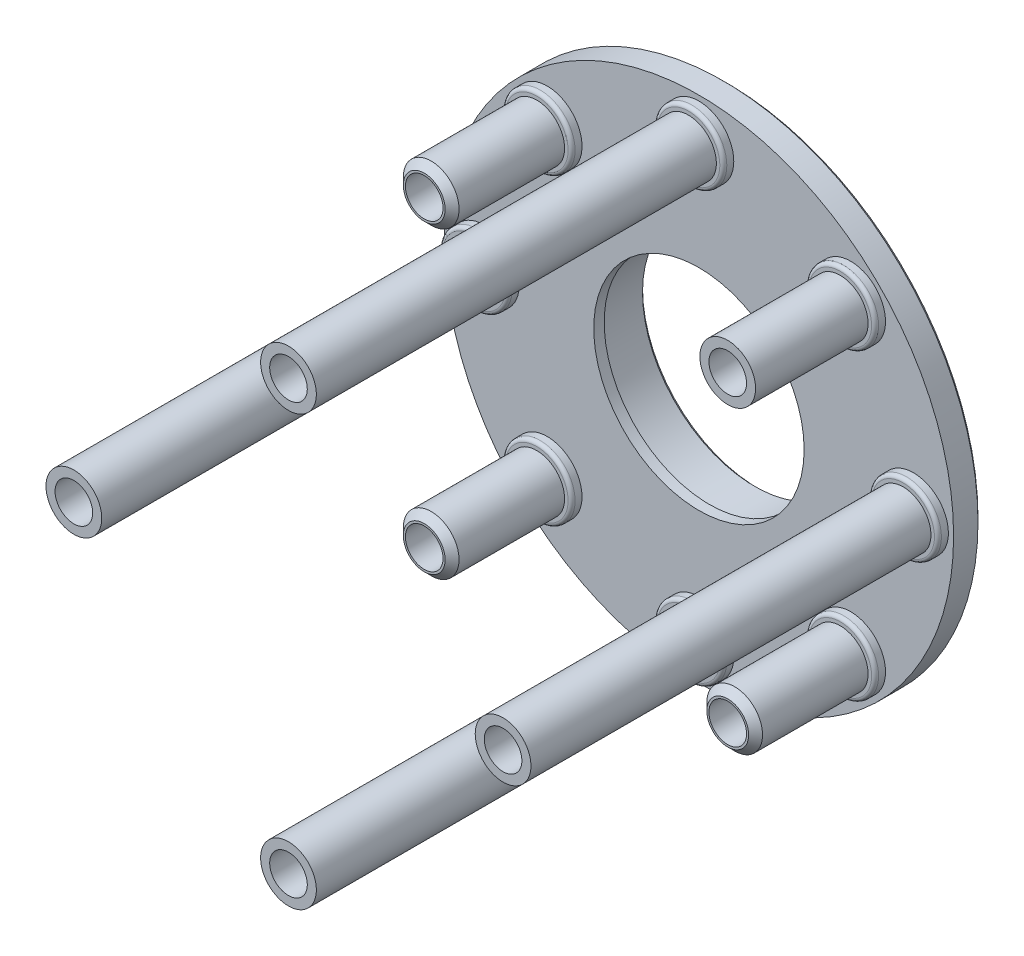
SolidWorks part; units mm, degrees
material "PLA"
ref_plane "Front Plane" through (0, 0, 0) normal (0, 0, 1) x (1, 0, 0)
ref_plane "Top Plane" through (0, 0, 0) normal (0, 1, 0) x (1, 0, 0)
ref_plane "Right Plane" through (0, 0, 0) normal (1, 0, 0) x (0, 0, -1)
sketch "Sketch1" plane through (0, 0, 0) normal (0, 0, 1) x (1, 0, 0)
  circle A0 centre (0, 0) radius 36.55
  circle A1 centre (0, 0) radius 30.8 construction
  circle A2 centre (0, 30.8) radius 2.7
  circle A3 centre (30.8, 0) radius 2.7
  circle A78 centre (0, -30.8) radius 2.7
  circle A79 centre (0, 30.8) radius 4.25 construction
  circle A80 centre (0, 0) radius 35.05 construction
  circle A94 centre (-30.8, 0) radius 2.7
  point P15 (0, 0)
  dimension "D2" = 61.6
  dimension "D3" = 5.4
  dimension "D5" = 8.5
  dimension "D1" = 1.5
  dimension "D4" = 4
extrude "Boss-Extrude1" add sketch "Sketch1" along normal blind 4
sketch "Sketch2" plane through (0, 0, 4) normal (0, 0, 1) x (1, 0, 0)
  circle A0 centre (0, 30.8) radius 4
  circle A2 centre (0, 30.8) radius 2.7 construction
  circle A5 centre (0, 30.8) radius 2.7
  point P15 (0, 0)
  dimension "D1" = 8
extrude "Boss-Extrude2" add sketch "Sketch2" along normal blind 58.9087
sketch "Sketch3" plane through (0, 0, 4) normal (0, 0, 1) x (1, 0, 0)
  arc A2 (5, 30.8) -> (5, 30.8) centre (0, 30.8) ccw
  circle A3 centre (0, 30.8) radius 5
  circle M5 centre (0, 30.8) radius 4
extrude "Boss-Extrude3" add sketch "Sketch3" along normal blind 1.5 contours A3 M5 region at (-4.8586, 30.8, 4)
sketch "Sketch4" plane through (0, 0, 4) normal (0, 0, 1) x (1, 0, 0)
  line L0 (0, 0) -> (-25.8448, 25.8448) construction
  line L1 (0, 0) -> (0, 30.8) construction
  circle A0 centre (0, 0) radius 36.55 construction
  circle A1 centre (0, 0) radius 36.55
  circle A2 centre (0, 30.8) radius 14 construction
  circle A6 centre (0, 0) radius 30.8 construction
  arc A8 (-15.3152, 33.1866) -> (-10.2972, 19.2148) centre (0, 30.8) ccw
  circle A9 centre (0, 0) radius 21.8
  circle A11 centre (0, 0) radius 16.8 construction
  arc A13 (-33.1866, 15.3152) -> (-19.2148, 10.2972) centre (-30.8, 0) cw
  circle A16 centre (0, 30.8) radius 15.5 construction
  point P15 (0, 0)
  point P25 (0, 0)
  dimension "D1" = 28
  dimension "D5" = 33.6
  dimension "D4" = 5
  dimension "D2" = 45
  dimension "D3" = 1.5
extrude "Boss-Extrude4" [suppressed] add sketch "Sketch4" along normal blind 58.9087 contours A1 A13 A9 A8
sketch "Sketch12" [suppressed] plane through (0, 0, 37.8382) normal (0, 0, 1) x (1, 0, 0)
  arc A0 (-11.2345, 15.816) -> (-15.816, 11.2345) centre (0, 0) ccw construction
  arc A1 (-11.2345, 15.816) -> (-15.816, 11.2345) centre (0, 0) ccw
  dimension "D1" = 6.4791
fillet "Fillet2" radius 0.5 1 edges at (5, 30.8, 5.5)
fillet "Fillet5" [suppressed] radius 1.6198
pattern_circular "CirPattern1" count 8 over 360 about axis through (0, 0, 4) along (0, 0, -1) of "Fillet2", "Boss-Extrude3", "Boss-Extrude2" reverse direction yes
ref_plane "Plane1" through (0, 0, 62.9087) normal (0, 0, 1) x (1, 0, 0)
chamfer "Chamfer1" distance 0.5 angle 45 1 edges at (36.55, 0, 0)
sketch "Sketch9" plane through (0, 0, 4) normal (0, 0, 1) x (1, 0, 0)
  circle A0 centre (0, 0) radius 8
  dimension "D1" = 16
extrude "Cut-Extrude4" cut sketch "Sketch9" against normal through all
sketch "Sketch10" plane through (0, 0, 0) normal (0, 0, -1) x (-1, 0, 0)
  circle A0 centre (0, 0) radius 8 construction
  circle A1 centre (0, 0) radius 8
  circle A2 centre (0, 0) radius 6.5
  dimension "D1" = 1.5
extrude "Boss-Extrude7" add sketch "Sketch10" against normal blind 6.5
sketch "Sketch13" plane through (0, 0, 0) normal (0, 1, 0) x (1, 0, 0)
  line L0 (0, 0) -> (0, -62.9087) construction
  line L1 (-4, -62.9087) -> (4, -62.9087) construction
  line L2 (19.0789, -4) -> (24.4789, -4) construction
  line L3 (-35, 0.5) -> (-45.6, -4) construction
  line L4 (-41.7615, -4) -> (-32.3392, 0)
  line L7 (36.05, 0) -> (-36.05, 0) construction
  line L8 (0, -4) -> (-45.6, -4) construction
  line L9 (-32.3392, 0) -> (-41.7615, 0)
  line L10 (-41.7615, 0) -> (-41.7615, -4)
  dimension "D1" = 35
  dimension "D2" = 45.6
  dimension "D3" = 4.5
  dimension "D4" = 1.5
sketch "Sketch14" plane through (0, 0, 4) normal (0, 0, 1) x (1, 0, 0)
  circle A0 centre (0, 0) radius 16.1
  circle A1 centre (0, 0) radius 6.5 construction
  dimension "D1" = 32.2
extrude "Cut-Extrude5" cut sketch "Sketch14" against normal through all both and the other way through all
sketch "Sketch15" plane through (0, 0, 4) normal (0, 0, 1) x (1, 0, 0)
  circle A0 centre (0, 0) radius 16.1
  circle A1 centre (0, 0) radius 15.1
  circle A2 centre (0, 0) radius 16.1 construction
  dimension "D1" = 1
extrude "Boss-Extrude8" add sketch "Sketch15" against normal blind 1.5
sketch "Sketch16" plane through (0, 0, 0) normal (0, 0, -1) x (-1, 0, 0)
  circle A0 centre (0, 0) radius 18.1
  circle A1 centre (0, 0) radius 16.1 construction
  circle M1 centre (0, 0) radius 16.1
extrude "Boss-Extrude9" add sketch "Sketch16" along normal blind 4.5 contours A0 M1 region at (17.5881, 0, 0)
chamfer "Chamfer3" distance 2 distance2 4.5 1 edges at (18.1, 0, 0) first distance on face at (18.1, 0, 0)
sketch "Sketch5" [suppressed] plane through (0, 0, 32.8234) normal (0, 0, 1) x (1, 0, 0)
  line L0 (0, 0) -> (-22.4506, 22.4506) construction
  line L1 (0, 0) -> (0, 26) construction
  circle A3 centre (-19.6222, 19.6222) radius 1.7
  circle A4 centre (0, 0) radius 31.75 construction
  arc A5 (-13.189, 28.881) -> (-28.881, 13.189) centre (0, 0) ccw construction
  dimension "D2" = 3.4
  dimension "D1" = 4
  dimension "D3" = 45
extrude "Cut-Extrude1" [suppressed] cut sketch "Sketch5" against normal through all
sketch "Sketch7" plane through (0, 0, 0) normal (0, 0, -1) x (-1, 0, 0)
  circle A0 centre (0, 30.8) radius 4.45
  circle A1 centre (0, 0) radius 30.8 construction
  point P15 (0, 0)
  dimension "D1" = 8.9
extrude "Cut-Extrude3" cut sketch "Sketch7" against normal blind 5 and the other way through all
sketch "Sketch6" [suppressed] plane through (0, 0, 0) normal (0, 0, -1) x (-1, 0, 0)
  circle A0 centre (19.6222, 19.6222) radius 2.95
  dimension "D1" = 5.9
extrude "Cut-Extrude2" [suppressed] cut sketch "Sketch6" against normal blind 3 and the other way through all
pattern_circular "CirPattern2" count 8 over 360 about axis through (0, 0, 4) along (0, 0, -1) of "Cut-Extrude3" reverse direction yes
chamfer "Chamfer4" distance 0.5 angle 45 1 edges at (-16.1, 0, -4.5)
sketch "Sketch17" plane through (0, 0, 62.9087) normal (0, 0, 1) x (1, 0, 0)
  circle A0 centre (-21.7789, 21.7789) radius 6.5962
extrude "Cut-Extrude6" cut sketch "Sketch17" against normal blind 41.2609
pattern_circular "CirPattern3" count 4 over 360 about axis through (0, 0, 4) along (0, 0, 1) of "Cut-Extrude6"
chamfer "Chamfer5" distance 1 angle 45 3 edges at (25.7789, -21.7789, 21.6477) (-17.7789, 21.7789, 21.6477) (-17.7789, -21.7789, 21.6477)
equation "\"Nr_s\" = 116"
equation "\"module\" = 0.7"
equation "\"pressure_angle\" = 20.0"
equation "\"h_a\" = 0.7"
equation "\"h_f\" = 0.875"
equation "\"clr_tip_root\" = 0.17500000000000004"
equation "\"dp_r_s\" = 81.19999999999999"
equation "\"db_r\"= \"dp_r_s\" * cos ( \"pressure_angle\" )'base CD"
equation "\"bearing_ID\" = 70"
equation "\"bearing_OD\" = 90"
equation "\"bearing_height\" = 10"
equation "\"clearance_planet\" = 1.5"
equation "\"case_dist\" = 6.5"
equation "\"Motor_case_OD_max\" = 131.3"
equation "\"case_mounting_PCD\" = 123.8"
equation "\"bearing mount thickness\" = 8"
equation "\"case_mounting_hole_dia\" = 3"
equation "\"output_mounting_PCD\" = 98"
equation "\"output_mounting_hole_dia\" = 4"
equation "\"clearance_case_mount_holes_shell_thickness\" = 1"
equation "\"motor_case_OD_base\" = 121.8"
equation "\"sec_carrier_thickness\" = 5"
equation "\"sun_coupler_hub_thickness\" = 4"
equation "\"clearance_sun_coupler_sec_carrier\" = 1.5"
equation "\"clearance_motor_and_case\" = 5"
equation "\"motor_OD\" = 106.8"
equation "\"Motor_case_thickness\" = 2.5"
equation "\"Motor_case_ID\" = 116.8"
equation "\"case_mounting_hole_shift\" = 1.0"
equation "\"output_mounting_nut_wrench_size\" = 7"
equation "\"output_mounting_nut_thickness\" = 3.2"
equation "\"case_mounting_hole_allen_socket_dia\" = 5.5"
equation "\"output_mounting_nut_depth\" = 3"
equation "\"case_mounting_bolt_depth\" = 4.5"
equation "\"Ns\" = 48"
equation "\"Np_b\" = 40"
equation "\"ring_radial_thickness\" = 5"
equation "\"ring_OD\"= \"Nr_s\" * \"module\" + \"ring_radial_thickness\" * 2"
equation "\"ring_to_chamfer_clearance\" = 1.5"
equation "\"Motor_case_OD_base_to_chamfer\" = 5"
equation "\"pattern_offset_from_motor_case_OD_base\" = 3"
equation "\"pattern_bulge_dia\" = 3"
equation "\"pattern_num_bulge\" = 18"
equation "\"pattern_depth\" = 2"
equation "\"motor_height\" = 47.6"
equation "\"case_mounting_wrench_size\" = 5.5"
equation "\"case_mounting_nut_clearance\" = 2"
equation "\"base_plate_thickness\" = 4"
equation "\"case_mounting_nut_thickness\" = 2.4"
equation "\"case_mounting_surface_height\" = 4"
equation "\"motor_mount_hole_PCD\" = 40"
equation "\"motor_mount_hole_dia\" = 5"
equation "\"motor_mount_hole_num\" = 4"
equation "\"central_hole_offset_from_motor_mount_PCD\" = 5"
equation "\"wire_slot_dist_from_center\" = 45.5"
equation "\"wire_slot_length\" = 10"
equation "\"wire_slot_radius\" = 3"
equation "\"driver_upper_holes_dist_from_center\" = 29"
equation "\"driver_lower_holes_dist_from_center\" = 13"
equation "\"driver_side_holes_dist_from_center\" = 22.5"
equation "\"driver_mount_holes_dia\" = 3"
equation "\"driver_mount_inserts_OD\" = 4.8"
equation "\"driver_mount_thickness\" = 1.5"
equation "\"driver_mount_height\" = 6"
equation "\"air_flow_hole_offset\" = 3"
equation "\"num_planet\" = 4"
equation "\"planet_pin_bolt_dia\" = 5"
equation "\"planet_pin_socket_head_dia\" = 8.5"
equation "\"carrier_PCD\" = 61.599999999999994"
equation "\"D2@Sketch1\"=\"carrier_PCD\""
equation "\"D3@Sketch1\"=\"planet_pin_bolt_dia\" + \"tight_clearance_3DP\""
equation "\"D4@Sketch1\"=\"num_planet\""
equation "\"D1@Boss-Extrude2\" = \"fw_p_s\" + \"clearance_planet\" * 2 + \"fw_p_b\""
equation "\"D1@Boss-Extrude3\"=\"clearance_planet\""
equation "\"D1@Sketch4\"=\"Np_b\"*\"module\""
equation "\"D3@Sketch4\"=\"clearance_planet\""
equation "\"D1@Boss-Extrude4\" = \"fw_p_s\" + \"clearance_planet\" * 2 + \"fw_p_b\""
equation "\"D1@Fillet2\"=\"clearance_planet\"/3"
equation "\"D1@CirPattern1\"=2*\"num_planet\""
equation "\"D1@CirPattern2\"=2*\"num_planet\""
equation "\"D1@Boss-Extrude7\"=\"bearing_height\"+ \"carrier_bearing_step_width\" - \"sun_shaft_bearing_width\""
equation "\"planet_shaft_dia\" = 8"
equation "\"D1@Sketch2\"= \"planet_shaft_dia\""
equation "\"planet_shaft_step_offset\" = 1"
equation "\"D1@Sketch3\"=\"planet_shaft_step_offset\""
equation "\"carrier_trapezoidal_support_sun_offset\" = 5"
equation "\"D4@Sketch4\"=\"carrier_trapezoidal_support_sun_offset\""
equation "\"carrier_trapezoidal_support_hole_PCD_offset_bearing_ID\" = 4"
equation "\"carrier_trapezoidal_support_hole_dia\" = 3"
equation "\"D2@Sketch5\"=\"carrier_trapezoidal_support_hole_dia\" + \"tight_clearance_3DP\""
equation "\"D1@Cut-Extrude2\"=\"carrier_trapezoidal_support_hole_dia\""
equation "\"carrier_trapezoidal_support_hole_socket_head_dia\" = 5.5"
equation "\"D1@Sketch6\"=\"carrier_trapezoidal_support_hole_socket_head_dia\" +  \"tight_clearance_3DP\""
equation "\"D1@Cut-Extrude3\"=\"planet_pin_bolt_dia\""
equation "\"D1@Sketch7\"=\"planet_pin_socket_head_dia\" + \"tight_clearance_3DP\""
equation "\"carrier_bearing_step_width\" = 1.5"
equation "\"standard_clearance_1_5mm\" = 1.5"
equation "\"standard_fillet_1_5mm\" = 1.5"
equation "\"sun_shaft_bearing_OD\" = 16"
equation "\"D1@Sketch9\"=\"sun_shaft_bearing_OD\""
equation "\"D1@Sketch10\"=\"standard_clearance_1_5mm\""
equation "\"sun_shaft_bearing_width\" = 5"
equation "\"standard_bearing_insertion_chamfer\" = 0.5"
equation "\"D1@Chamfer1\"=\"standard_bearing_insertion_chamfer\""
equation "\"D5@Sketch4\"=\"Ns\"*\"module\""
equation "\"D1@Sketch5\"=\"carrier_trapezoidal_support_hole_PCD_offset_bearing_ID\""
equation "\"D1@Plane1\" = \"fw_p_s\" + \"clearance_planet\" * 2 + \"fw_p_b\""
equation "\"D2@Sketch4\"=180/\"num_planet\""
equation "\"D3@Sketch5\"=180/\"num_planet\""
equation "\"carrier_trapezoidal_support_hole_wrench_size\" = 5.5"
equation "\"planet_pin_bolt_wrench_size\" = 8"
equation "\"pressure angle\" = 20.0"
equation "\"h_b\" = 0.875"
equation "\"dp_s\" = 33.599999999999994"
equation "\"db_s\" = 31.57367205840652"
equation "\"fw_s_calc\" = 5.685933367726717"
equation "\"alpha_s\" = 0.8539582918412343"
equation "\"beta_s\" = 2.0420834163175314"
equation "\"dp_p_b\" = 28.0"
equation "\"db_p_b\" = 26.311393382005434"
equation "\"fw_p_s\" = 25.912913082891553"
equation "\"alpha_p_b\" = 0.8539582918412485"
equation "\"beta_p_b\" = 2.792083416317503"
equation "\"planet_bearing_OD\" = 12"
equation "\"planet_bearing_width\" = 3.5"
equation "\"planet_bore\" = 10"
equation "\"motor_output_hole_PCD\" = 23"
equation "\"motor_output_hole_dia\" = 4"
equation "\"motor_output_hole_num\" = 4"
equation "\"sun_shaft_bearing_ID\" = 8"
equation "\"sun_hub_dia\" = 30.0"
equation "\"sun_central_bolt_dia\" = 5"
equation "\"sun_central_bolt_socket_head_dia\" = 8.5"
equation "\"fw_s_used\" = 63.40868620995457"
equation "\"motor_output_hole_CSK_OD\" = 8"
equation "\"motor_output_hole_CSK_head_height\" = 2.0"
equation "\"bearing_retainer_thickness\" = 2"
equation "\"Np_s\" = 28"
equation "\"fw_p_b\" = 29.99577312706301"
equation "\"dp_p_s\" = 19.599999999999998"
equation "\"db_p_s\" = 18.417975367403802"
equation "\"alpha_p_s\" = 0.8539582918412592"
equation "\"beta_p_s\" = 4.7206548448889105"
equation "\"D1@Fillet5\"= \"D1@Sketch12\" / 4"
equation "\"Nr_b\" = 128"
equation "\"dp_r_b\" = 89.6"
equation "\"db_r_b\" = 84.19645882241738"
equation "\"fw_r_b\" = 29.99577312706301"
equation "\"alpha_r_b\" = 0.8539582918412556"
equation "\"beta_r_b\" = 3.114166583682511"
equation "\"ring_OD_b\" = 99.6"
equation "\"Fillet10\"= IIF ( \"ring_OD_b\" > ( \"bearing_OD\" + 2 * \"bearing mount thickness\" ) , \"suppressed\" , \"unsuppressed\" )"
equation "\"Fillet11\"= IIF ( \"ring_OD_b\" < ( \"bearing_OD\" + 2 * \"bearing mount thickness\" ) , \"suppressed\" , \"unsuppressed\" )"
equation "\"clr_tip_root_s\" = 0.17500000000000004"
equation "\"db_r_s\" = 76.30304080781575"
equation "\"fw_r_s\" = 24.412913082891553"
equation "\"alpha_r_s\" = 0.8539582918412556"
equation "\"beta_r_s\" = 3.259640721613546"
equation "\"D1@Sketch13\"=\"bearing_ID\"/2"
equation "\"D2@Sketch13\"=(\"Nr_s\"*\"module\"+\"ring_radial_thickness\"*2)*0.5"
equation "\"D3@Sketch13\"=\"standard_clearance_1_5mm\"*3"
equation "\"D4@Sketch13\"=\"standard_clearance_1_5mm\""
equation "\"D5@Sketch1\"=\"planet_pin_socket_head_dia\""
equation "\"D1@Sketch1\"=\"standard_clearance_1_5mm\""
equation "\"small_ring_case_thickness\" = 4"
equation "\"carrier_thickness\" = 4"
equation "\"small_ring_output_wall_thickness\" = 5"
equation "\"small_ring_output_wall_to_bearing_shaft_attachement_hole_dia\" = 4"
equation "\"small_ring_output_wall_to_bearing_shaft_attachement_hole_depth\" = 6.5"
equation "\"small_ring_output_wall_to_bearing_shaft_attachement_nut_wrench\" = 7"
equation "\"small_ring_output_wall_to_bearing_shaft_attachement_nut_thickness\" = 3.2"
equation "\"small_ring_output_wall_to_bearing_shaft_attachement_hole_pcd\" = 12"
equation "\"small_ring_output_wall_to_bearing_shaft_attachement_hole_num\" = 3"
equation "\"small_ring_output_wall_to_bearing_shaft_attachement_hole_CSK_OD\" = 8"
equation "\"small_ring_output_wall_to_bearing_shaft_attachement_hole_CSK_head_height\" = 2.0"
equation "\"carrier_small_ring_inner_bearing_ID\" = 20"
equation "\"carrier_small_ring_inner_bearing_OD\" = 32"
equation "\"carrier_small_ring_inner_bearing_height\" = 7"
equation "\"carrier_small_ring_inner_bearing_flap\" = 2"
equation "\"gear_casing_big_ring_to_bearing_dist\" = 34.91291308289155"
equation "\"gear_casing_thickness\" = 4"
equation "\"D1@Boss-Extrude1\"=\"carrier_thickness\""
equation "\"D1@Boss-Extrude9\"= \"carrier_small_ring_inner_bearing_height\" - \"carrier_thickness\" + \"standard_clearance_1_5mm\""
equation "\"D3@Chamfer3\"=\"carrier_small_ring_inner_bearing_height\"-\"carrier_thickness\" + \"standard_clearance_1_5mm\""
equation "\"D1@Chamfer3\"=\"standard_clearance_1_5mm\"*4/3"
equation "\"D1@Sketch14\"=\"carrier_small_ring_inner_bearing_OD\" + \"tight_clearance_3DP\"/2"
equation "\"D1@Sketch16\"=\"standard_clearance_1_5mm\"*4/3"
equation "\"tight_clearance_3DP\" = 0.4"
equation "\"loose_clearance_3DP\" = 0.8"
equation "\"D1@Chamfer4\"= \"standard_bearing_insertion_chamfer\""
equation "\"D1@Cut-Extrude6\"=\"fw_p_s\" + \"clearance_planet\" * 2 + \"fw_p_b\" - \"fw_idler\"-3mm"
equation "\"D1@CirPattern3\"=\"num_planet\""
equation "\"Ns_fs\" = 60"
equation "\"dp_fs\" = 42.0"
equation "\"db_fs\" = 39.46709007300815"
equation "\"alpha_fs\" = 0.8539582918412592"
equation "\"beta_fs\" = 1.2920834163174817"
equation "\"fw_fs\" = 25.912913082891553"
equation "\"num_idler\" = 4"
equation "\"idler_angle_offset\" = 45.0"
equation "\"fs_bore_dia\" = 31.599999999999998"
equation "\"fs_bore_wall\" = 2.6500000000000004"
equation "\"fs_axial_clearance\" = 0.8"
equation "\"fw_idler\" = 14.647747849734928"
